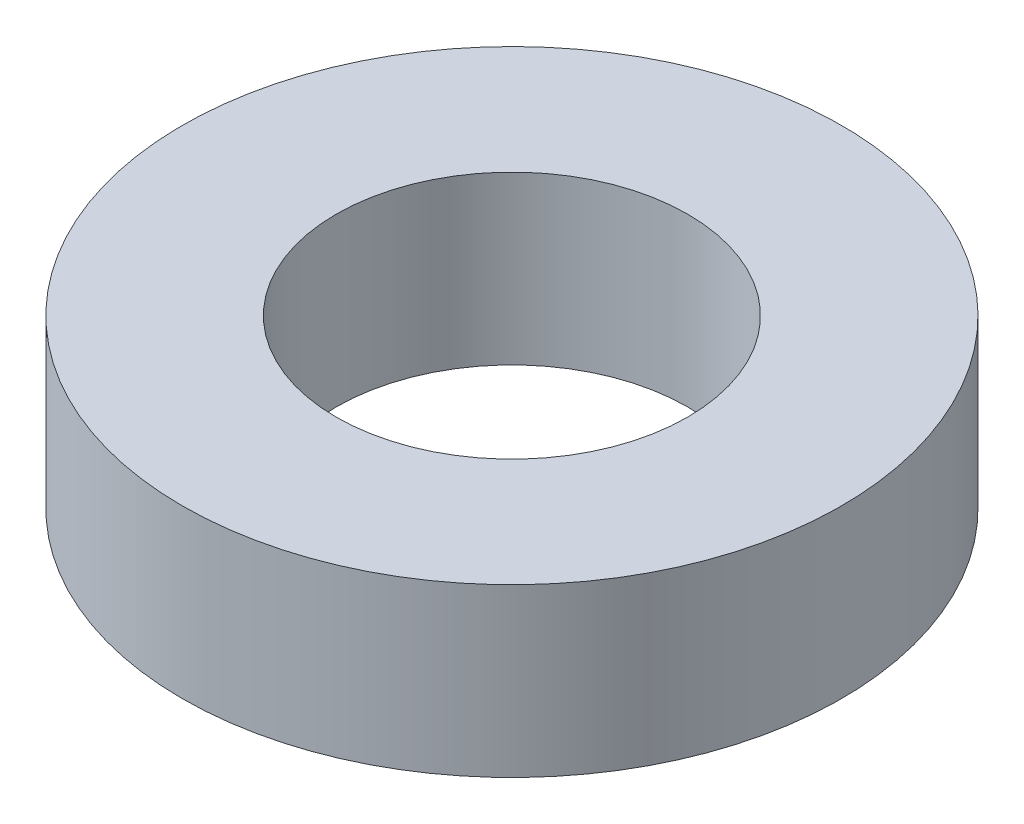
SolidWorks part; units mm, degrees
ref_plane "Front Plane" through (0, 0, 0) normal (0, 0, 1) x (1, 0, 0)
ref_plane "Top Plane" through (0, 0, 0) normal (0, 1, 0) x (1, 0, 0)
ref_plane "Right Plane" through (0, 0, 0) normal (1, 0, 0) x (0, 0, -1)
sketch "Sketch1" plane through (0, 0, 0) normal (0, 1, 0) x (1, 0, 0)
  circle A0 centre (0, 0) radius 37.5
  dimension "FLANGE_OD" = 75
extrude "Boss-Extrude1" add sketch "Sketch1" along normal blind 19
sketch "Sketch2" plane through (0, 0, 0) normal (0, 1, 0) x (1, 0, 0)
  circle A0 centre (0, 0) radius 20
  dimension "BORE_D" = 40
extrude "Cut-Extrude1" cut sketch "Sketch2" along normal through all
sketch "Sketch3" plane through (0, 19, 0) normal (0, 1, 0) x (1, 0, 0)
  circle A0 centre (0, 0) radius 14.3842 construction
  circle A1 centre (-14.3842, 0) radius 2.6002
  dimension "BOLT_D" = 5.2003
  dimension "BOLT_PCD" = 28.7683
extrude "Cut-Extrude2" cut sketch "Sketch3" against normal blind 14.0199 rebuild error yes
pattern_circular "CirPattern1" count 6 over 360 rebuild error yes
